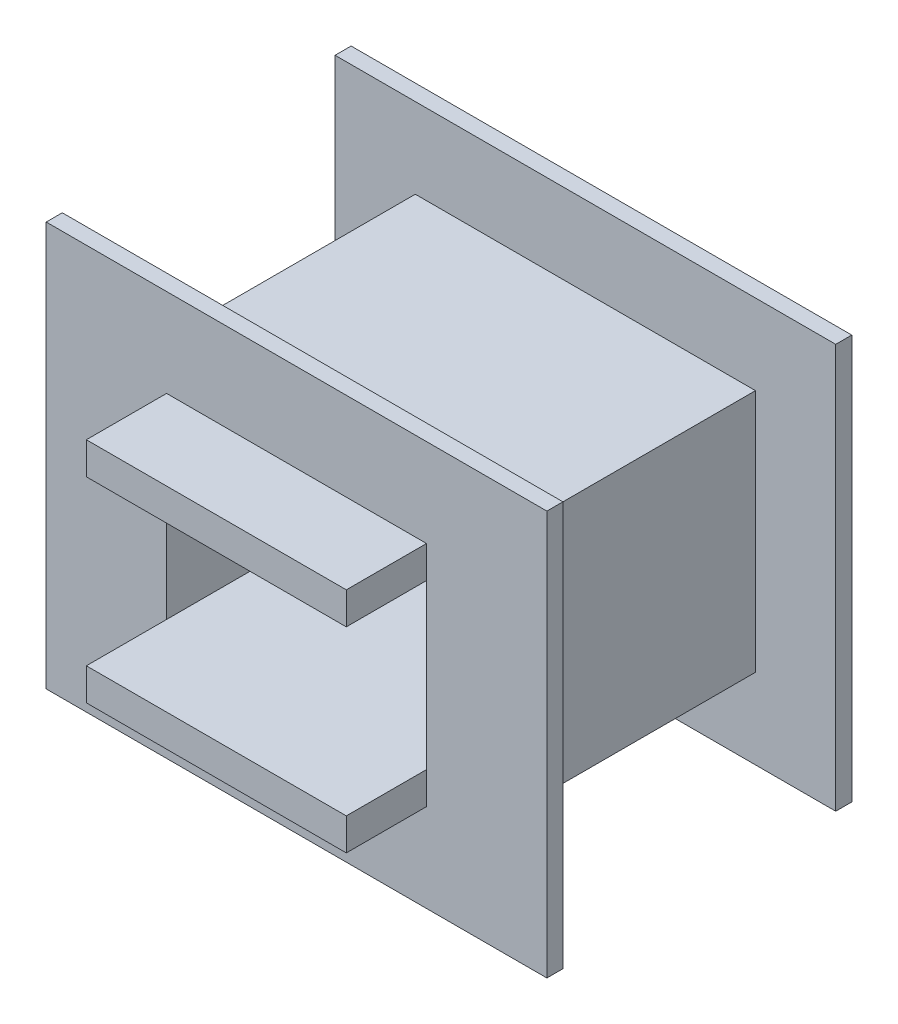
SolidWorks part; units mm, degrees
material "Nylon 101"
ref_plane "Front Plane" through (0, 0, 0) normal (0, 0, 1) x (1, 0, 0)
ref_plane "Top Plane" through (0, 0, 0) normal (0, 1, 0) x (1, 0, 0)
ref_plane "Right Plane" through (0, 0, 0) normal (1, 0, 0) x (0, 0, -1)
sketch "Sketch1" plane through (0, 0, 0) normal (0, 0, 1) x (1, 0, 0)
  line L0 (-8.1, -5.1) -> (8.1, 5.1) construction
  line L4 (-15.6, -12.6) -> (15.6, -12.6)
  line L5 (15.6, -12.6) -> (15.6, 12.6)
  line L6 (15.6, 12.6) -> (-15.6, 12.6)
  line L7 (-15.6, 12.6) -> (-15.6, -12.6)
  line L12 (-8.1, -5.1) -> (8.1, -5.1)
  line L13 (8.1, -5.1) -> (8.1, 5.1)
  line L14 (8.1, 5.1) -> (-8.1, 5.1)
  line L15 (-8.1, 5.1) -> (-8.1, -5.1)
  point P8 (0, 0)
  dimension "D1" = 10.2
  dimension "D3" = 16.2
  dimension "D2" = 7.5
extrude "Boss-Extrude1" add sketch "Sketch1" along normal blind 9.5 and the other way blind 9.5
sketch "Sketch2" plane through (0, 12.6, 0) normal (0, 1, 0) x (1, 0, 0)
  line L0 (-15.6, 9.5) -> (-15.6, -9.5) construction
  line L1 (-15.6, 8.5) -> (15.6, 8.5)
  line L2 (-15.6, 8.5) -> (-15.6, -8.5)
  line L3 (-15.6, -8.5) -> (15.6, -8.5)
  line L4 (15.6, 8.5) -> (15.6, -8.5)
  line L5 (15.6, 9.5) -> (15.6, -9.5) construction
  line L6 (15.6, 8.5) -> (-15.6, -8.5) construction
  line L7 (15.6, 9.5) -> (-15.6, 9.5) construction
  dimension "D1" = 1
extrude "Cut-Extrude1" cut sketch "Sketch2" against normal blind 5
mirror "Mirror1" about plane through (0, 0, 0) normal (0, 1, 0) of "Cut-Extrude1"
sketch "Sketch3" plane through (15.6, 0, 0) normal (1, 0, 0) x (0, 0, -1)
  line L1 (-8.5, 7.6) -> (8.5, 7.6)
  line L2 (-8.5, 7.6) -> (-8.5, -7.6)
  line L3 (-8.5, -7.6) -> (8.5, -7.6)
  line L4 (8.5, 7.6) -> (8.5, -7.6)
extrude "Cut-Extrude2" cut sketch "Sketch3" against normal blind 5
mirror "Mirror2" about plane through (0, 0, 0) normal (1, 0, 0) of "Cut-Extrude2"
sketch "Sketch4" plane through (0, 0, 9.5) normal (0, 0, 1) x (1, 0, 0)
  line L1 (-8.1, 5.1) -> (8.1, 5.1)
  line L2 (-8.1, 5.1) -> (-8.1, 7.1)
  line L3 (-8.1, 7.1) -> (8.1, 7.1)
  line L4 (8.1, 5.1) -> (8.1, 7.1)
  line L5 (8.1, -5.1) -> (-8.1, -5.1)
  line L6 (8.1, -5.1) -> (8.1, -7.1)
  line L7 (8.1, -7.1) -> (-8.1, -7.1)
  line L8 (-8.1, -5.1) -> (-8.1, -7.1)
  dimension "D1" = 2
extrude "Boss-Extrude2" add sketch "Sketch4" along normal blind 5
mirror "Mirror3" about plane through (0, 0, 0) normal (0, 0, 1) of "Boss-Extrude2"
sketch "Sketch6" plane through (0, 7.1, 0) normal (0, 1, 0) x (1, 0, 0)
  line L1 (-8.1, 14.5) -> (8.1, 14.5)
  line L2 (-8.1, 14.5) -> (-8.1, 9.5)
  line L3 (-8.1, 9.5) -> (8.1, 9.5)
  line L4 (8.1, 14.5) -> (8.1, 9.5)
extrude "Cut-Extrude3" cut sketch "Sketch6" against normal blind 2
